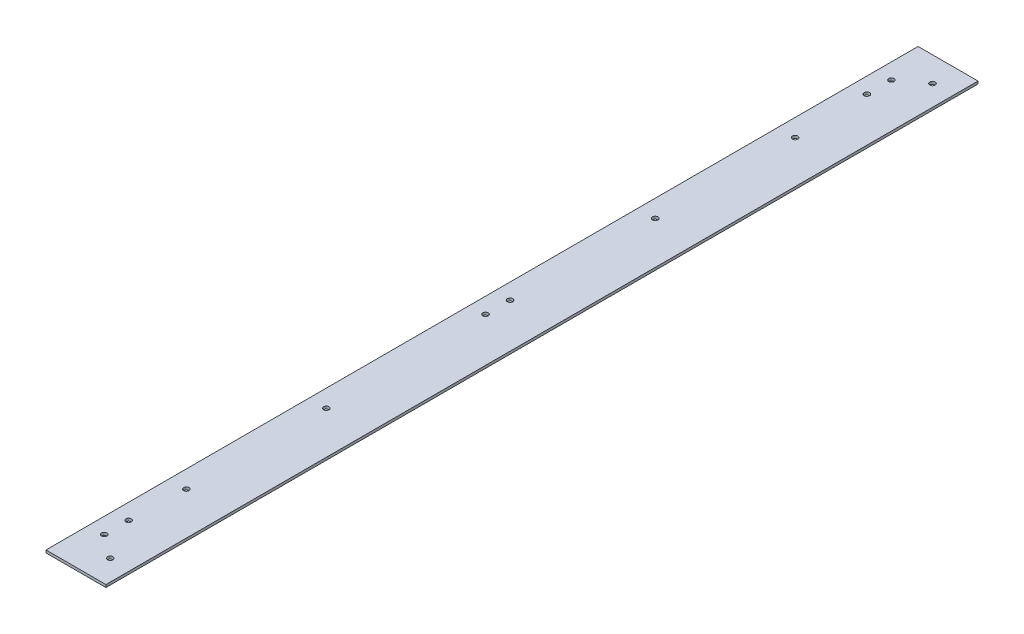
SolidWorks part; units mm, degrees
ref_plane "Alzado" through (0, 0, 0) normal (0, 0, 1) x (1, 0, 0)
ref_plane "Planta" through (0, 0, 0) normal (0, 1, 0) x (1, 0, 0)
ref_plane "Vista lateral" through (0, 0, 0) normal (1, 0, 0) x (0, 0, -1)
sketch "Croquis1" plane through (0, 0, 0) normal (0, 1, 0) x (1, 0, 0)
  line L1 (0, 0) -> (35, 0)
  line L2 (0, 0) -> (0, -500)
  line L3 (0, -500) -> (35, -500)
  line L4 (35, 0) -> (35, -500)
  dimension "D1" = 35
  dimension "D2" = 500
extrude "Saliente-Extruir1" add sketch "Croquis1" along normal blind 1.5
sketch "Croquis2" plane through (0, 1.5, 0) normal (0, 1, 0) x (1, 0, 0)
  line L0 (35, 0) -> (0, 0) construction
  line L1 (35, -500) -> (35, 0) construction
  line L2 (0, -500) -> (35, -500) construction
  circle A0 centre (22.5, -15) radius 1.55
  circle A1 centre (22.5, -485) radius 1.55
  dimension "D1" = 3.1
  dimension "D2" = 15
  dimension "D4" = 3.1
  dimension "D3" = 12.5
  dimension "D5" = 15
  dimension "D6" = 12.5
extrude "Cortar-Extruir1" cut sketch "Croquis2" against normal up to surface (1.5 mm away) up to face at (17.5, 0, 250)
sketch "Croquis3" plane through (0, 1.5, 0) normal (0, 1, 0) x (1, 0, 0)
  line L0 (0, 0) -> (0, -500) construction
  line L1 (35, 0) -> (0, 0) construction
  line L2 (0, -500) -> (35, -500) construction
  line L3 (0, 0) -> (0, -500) construction
  line L4 (35, -250) -> (0, -250) construction
  line L5 (35, -500) -> (35, 0) construction
  line L6 (35, 0) -> (0, 0) construction
  circle A0 centre (9, -25) radius 1.55
  circle A1 centre (9, -39) radius 1.55
  circle A2 centre (9, -475) radius 1.55
  circle A3 centre (9, -461) radius 1.55
  circle A4 centre (9, -243) radius 1.55
  circle A5 centre (9, -257) radius 1.55
  dimension "D1" = 3.1
  dimension "D5" = 3.1
  dimension "D10" = 7
  dimension "D2" = 14
  dimension "D3" = 9
  dimension "D4" = 25
  dimension "D6" = 14
  dimension "D7" = 25
  dimension "D8" = 9
  dimension "D9" = 250
  dimension "D11" = 7
extrude "Cortar-Extruir2" cut sketch "Croquis3" against normal up to surface (1.5 mm away) up to face at (22.5, 0, 16.55)
sketch "Croquis5" plane through (0, 1.5, 0) normal (0, 1, 0) x (1, 0, 0)
  line L0 (0, -500) -> (35, -500) construction
  line L1 (35, -500) -> (35, 0) construction
  line L2 (35, 0) -> (0, 0) construction
  circle A0 centre (10, -81) radius 1.55
  circle A1 centre (10, -161) radius 1.55
  circle A2 centre (10, -349) radius 1.55
  circle A3 centre (10, -429) radius 1.55
  dimension "D1" = 3.1
  dimension "D7" = 71
  dimension "D2" = 80
  dimension "D3" = 80
  dimension "D4" = 25
  dimension "D5" = 25
  dimension "D6" = 81
extrude "Cortar-Extruir3" cut sketch "Croquis5" against normal up to surface (1.5 mm away) up to face at (9, 0, 26.55)
sketch "Croquis6" plane through (0, 1.5, 0) normal (0, 1, 0) x (1, 0, 0)
  line L8 (0.75, -0.75) -> (0.75, -499.25)
  line L9 (0.75, -499.25) -> (34.25, -499.25)
  line L10 (34.25, -499.25) -> (34.25, -0.75)
  line L11 (34.25, -0.75) -> (0.75, -0.75)
  line L12 (0.75, -0.75) -> (0.75, -499.25)
  line L13 (0.75, -499.25) -> (34.25, -499.25)
  line L14 (34.25, -499.25) -> (34.25, -0.75)
  line L15 (34.25, -0.75) -> (0.75, -0.75)
  dimension "D1" = 0.75
extrude "Cortar-Extruir4" cut sketch "Croquis6" against normal up to surface (1.5 mm away) flip side to cut up to face at (10, 0, 82.55)
sketch "Croquis7" plane through (0, 1.5, 0) normal (0, 1, 0) x (1, 0, 0)
  line L1 (0.75, -0.75) -> (0, -0.75)
  line L2 (0.75, -0.75) -> (0.75, -499.25)
  line L3 (0.75, -499.25) -> (0, -499.25)
  line L4 (0, -0.75) -> (0, -499.25)
  dimension "D1" = 0.75
extrude "Saliente-Extruir2" add sketch "Croquis7" against normal up to surface (1.5 mm away) up to face at (22.5, 0, 486.55)
